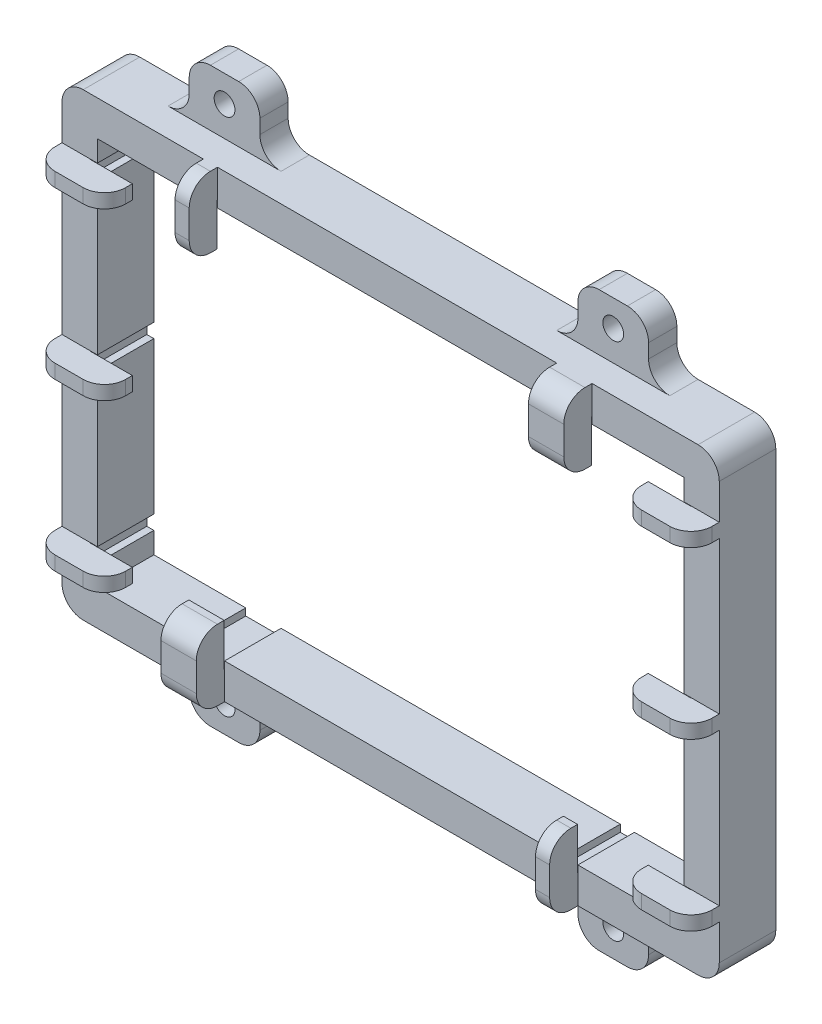
SolidWorks part; units mm, degrees
ref_plane "Front Plane" through (0, 0, 0) normal (0, 0, 1) x (1, 0, 0)
ref_plane "Top Plane" through (0, 0, 0) normal (0, 1, 0) x (1, 0, 0)
ref_plane "Right Plane" through (0, 0, 0) normal (1, 0, 0) x (0, 0, -1)
sketch "Sketch1" plane through (0, 0, 0) normal (0, 0, 1) x (1, 0, 0)
  line L0 (-41.5, 29.0054) -> (-46.5, 32.5) construction
  line L1 (41.5, -27.5) -> (-41.5, -27.5)
  line L2 (41.5, -27.5) -> (41.5, 27.5)
  line L3 (41.5, 27.5) -> (-41.5, 27.5)
  line L4 (-41.5, -27.5) -> (-41.5, 27.5)
  line L5 (0, -62.4654) -> (0, 68.7423) construction
  line L6 (-81.6773, -1.5) -> (70.6517, -1.5) construction
  line L7 (46.5, -32.5) -> (-46.5, -32.5)
  line L8 (46.5, -32.5) -> (46.5, 32.5)
  line L9 (46.5, 32.5) -> (-46.5, 32.5)
  line L10 (-46.5, -32.5) -> (-46.5, 32.5)
  line L11 (46.5, -32.5) -> (41.5, -29.0054) construction
  line L12 (46.5, 32.5) -> (41.5, 29.0054) construction
  line L13 (-41.5, -29.0054) -> (-46.5, -32.5) construction
  point P0 (0, 0)
  point P6 (0, 0)
  dimension "D1" = 83
  dimension "D2" = 55
  dimension "D3" = 5
  dimension "D4" = 5
  dimension "D5" = 5
  dimension "D6" = 5
extrude "Boss-Extrude1" add sketch "Sketch1" along normal blind 8
fillet "Fillet1" radius 3 4 edges at (-46.5, -32.5, 4) (-46.5, 32.5, 4) (46.5, -32.5, 4) (46.5, 32.5, 4)
sketch "Sketch2" plane through (0, 32.5, 0) normal (0, 1, 0) x (1, 0, 0)
  line L0 (-43.5, 0) -> (-43.5, -8) construction
  line L1 (-32.5, 0) -> (-22.5, 0)
  line L2 (-32.5, 0) -> (-32.5, -4)
  line L3 (-32.5, -4) -> (-22.5, -4)
  line L4 (-22.5, 0) -> (-22.5, -4)
  line L5 (-32.5, 0) -> (-22.5, -4) construction
  line L6 (-32.5, -4) -> (-22.5, 0) construction
  line L7 (22.5, 0) -> (32.5, 0)
  line L8 (22.5, 0) -> (22.5, -4)
  line L9 (22.5, -4) -> (32.5, -4)
  line L10 (32.5, 0) -> (32.5, -4)
  line L11 (22.5, 0) -> (32.5, -4) construction
  line L12 (22.5, -4) -> (32.5, 0) construction
  line L13 (43.5, -8) -> (43.5, 0) construction
  line L16 (43.5, 0) -> (-43.5, 0) construction
  line L17 (43.5, -8) -> (-43.5, -8) construction
  point P0 (-27.5, -2)
  point P5 (27.5, -2)
  dimension "D1" = 10
  dimension "D2" = 10
  dimension "D3" = 11
  dimension "D4" = 11
  dimension "D5" = 0
  dimension "D6" = 0
  dimension "D7" = 4
  dimension "D8" = 4
extrude "Boss-Extrude6" add sketch "Sketch2" along normal blind 8
mirror "Mirror2" about plane through (0, 0, 0) normal (0, 1, 0) of "Boss-Extrude6"
fillet "Fillet3" radius 3 8 edges at (32.5, -32.5, 2) (22.5, -32.5, 2) (-22.5, -32.5, 2) (-32.5, -32.5, 2) (-32.5, 32.5, 2) (-22.5, 32.5, 2) (22.5, 32.5, 2) (32.5, 32.5, 2)
sketch "Sketch9" plane through (0, 0, 4) normal (0, 0, 1) x (1, 0, 0)
  circle A1 centre (27.5, -36.7427) radius 1.47
  dimension "D1" = 2.94
extrude "Cut-Extrude1" cut sketch "Sketch9" against normal through all
mirror "Mirror3" about plane through (0, 0, 0) normal (1, 0, 0) of "Cut-Extrude1"
mirror "Mirror4" about plane through (0, 0, 0) normal (0, 1, 0) of "Mirror3"
sketch "Sketch10" plane through (0, 0, 0) normal (0, 0, -1) x (-1, 0, 0)
  line L0 (41.5, -27.5) -> (-41.5, -27.5) construction
  line L1 (-24.5, -27.5) -> (-26.5, -27.5)
  line L2 (-24.5, -27.5) -> (-24.5, -28.5)
  line L3 (-24.5, -28.5) -> (-26.5, -28.5)
  line L4 (-26.5, -27.5) -> (-26.5, -28.5)
  line L5 (-41.5, -27.5) -> (-41.5, 27.5) construction
  line L7 (23.5, -27.5) -> (28.5, -27.5)
  line L8 (23.5, -27.5) -> (23.5, -28.5)
  line L9 (23.5, -28.5) -> (28.5, -28.5)
  line L10 (28.5, -27.5) -> (28.5, -28.5)
  line L13 (41.5, 27.5) -> (41.5, -27.5) construction
  dimension "D1" = 1
  dimension "D2" = 2
  dimension "D3" = 15
  dimension "D4" = 13
  dimension "D5" = 5
  dimension "D6" = 1
fillet "Fillet4" radius 3 8 edges at (-22.5, 40.5, 2) (-32.5, 40.5, 2) (22.5, 40.5, 2) (32.5, 40.5, 2) (32.5, -40.5, 2) (22.5, -40.5, 2) (-22.5, -40.5, 2) (-32.5, -40.5, 2)
extrude "Cut-Extrude2" cut sketch "Sketch10" against normal through all
sketch "Sketch11" plane through (0, 0, 0) normal (0, 0, -1) x (-1, 0, 0)
  line L0 (41.5, 27.5) -> (26.5, 27.5) construction
  line L1 (-41.5, 27.5) -> (41.5, 27.5) construction
  line L2 (-41.5, 27.5) -> (-28.5, 27.5) construction
  line L3 (26.5, 27.5) -> (24.5, 27.5)
  line L4 (26.5, 27.5) -> (26.5, 28.5)
  line L5 (26.5, 28.5) -> (24.5, 28.5)
  line L6 (24.5, 27.5) -> (24.5, 28.5)
  line L8 (-28.5, 27.5) -> (-23.5, 27.5)
  line L9 (-28.5, 27.5) -> (-28.5, 28.5)
  line L10 (-28.5, 28.5) -> (-23.5, 28.5)
  line L11 (-23.5, 27.5) -> (-23.5, 28.5)
  dimension "D1" = 15
  dimension "D2" = 2
  dimension "D3" = 1
  dimension "D4" = 13
  dimension "D5" = 1
  dimension "D6" = 5
extrude "Cut-Extrude3" cut sketch "Sketch11" against normal through all
sketch "Sketch12" plane through (0, 0, 0) normal (0, 0, -1) x (-1, 0, 0)
  line L0 (58.5237, 0) -> (-57.2606, 0) construction
  line L6 (-41.5, -27.5) -> (-41.5, 27.5) construction
  line L11 (-42.5, 1) -> (-41.5, 1)
  line L12 (-42.5, 1) -> (-42.5, -1)
  line L13 (-42.5, -1) -> (-41.5, -1)
  line L14 (-41.5, 1) -> (-41.5, -1)
  line L15 (-42.5, 1) -> (-41.5, -1) construction
  line L16 (-42.5, -1) -> (-41.5, 1) construction
  line L17 (-41.5, -27.5) -> (-41.5, -24.5) construction
  line L18 (-41.5, 27.5) -> (-41.5, 24.5) construction
  line L19 (-41.5, -24.5) -> (-42.5, -24.5)
  line L20 (-41.5, -24.5) -> (-41.5, -22.5)
  line L21 (-41.5, -22.5) -> (-42.5, -22.5)
  line L22 (-42.5, -24.5) -> (-42.5, -22.5)
  line L24 (-41.5, 24.5) -> (-42.5, 24.5)
  line L25 (-41.5, 24.5) -> (-41.5, 22.5)
  line L26 (-41.5, 22.5) -> (-42.5, 22.5)
  line L27 (-42.5, 24.5) -> (-42.5, 22.5)
  point P3 (-42, 0)
  dimension "D1" = 2
  dimension "D2" = 1
  dimension "D3" = 3
  dimension "D4" = 1
  dimension "D5" = 2
  dimension "D6" = 3
  dimension "D7" = 1
  dimension "D8" = 2
extrude "Cut-Extrude4" cut sketch "Sketch12" against normal through all
mirror "Mirror5" about plane through (0, 0, 0) normal (1, 0, 0) of "Cut-Extrude4"
sketch "Sketch14" plane through (0, 0, 8) normal (0, 0, 1) x (1, 0, 0)
  line L0 (46.5, -29.5) -> (46.5, 29.5) construction
  line L1 (42.5, 22.5) -> (46.5, 22.5)
  line L2 (42.5, 22.5) -> (42.5, 24.5)
  line L3 (42.5, 24.5) -> (46.5, 24.5)
  line L4 (46.5, 22.5) -> (46.5, 24.5)
  line L6 (42.5, -1) -> (46.5, -1)
  line L7 (42.5, -1) -> (42.5, 1)
  line L8 (42.5, 1) -> (46.5, 1)
  line L9 (46.5, -1) -> (46.5, 1)
  line L10 (42.5, -24.5) -> (46.5, -24.5)
  line L11 (42.5, -24.5) -> (42.5, -22.5)
  line L12 (42.5, -22.5) -> (46.5, -22.5)
  line L13 (46.5, -24.5) -> (46.5, -22.5)
  dimension "D1" = 2
  dimension "D2" = 2
  dimension "D3" = 2
extrude "Boss-Extrude14" add sketch "Sketch14" along normal blind 4
mirror "Mirror6" about plane through (0, 0, 0) normal (1, 0, 0) of "Boss-Extrude14"
sketch "Sketch15" plane through (42.5, 0, 0) normal (-1, 0, 0) x (0, 0, 1)
  line L0 (8, 24.5) -> (0, 24.5) construction
  line L5 (8.05, 24.5) -> (12, 24.5)
  line L6 (8.05, 24.5) -> (8.05, 22.5)
  line L7 (8.05, 22.5) -> (12, 22.5)
  line L8 (12, 24.5) -> (12, 22.5)
  line L14 (12, -1) -> (8, -1) construction
  line L15 (12, 1) -> (8.05, 1)
  line L16 (12, 1) -> (12, -1)
  line L17 (12, -1) -> (8.05, -1)
  line L18 (8.05, 1) -> (8.05, -1)
  line L19 (12, -24.5) -> (8, -24.5) construction
  line L20 (12, -22.5) -> (8.05, -22.5)
  line L21 (12, -22.5) -> (12, -24.5)
  line L22 (12, -24.5) -> (8.05, -24.5)
  line L23 (8.05, -22.5) -> (8.05, -24.5)
  dimension "D1" = 3.95
  dimension "D2" = 3.95
  dimension "D3" = 3.95
extrude "Boss-Extrude18" add sketch "Sketch15" along normal blind 6
mirror "Mirror7" about plane through (0, 0, 0) normal (1, 0, 0) of "Boss-Extrude18"
sketch "Sketch16" plane through (0, 0, 8) normal (0, 0, 1) x (1, 0, 0)
  line L0 (43.5, 32.5) -> (-43.5, 32.5) construction
  line L1 (-26.5, 28.5) -> (-24.5, 28.5)
  line L2 (-26.5, 28.5) -> (-26.5, 32.5)
  line L3 (-26.5, 32.5) -> (-24.5, 32.5)
  line L4 (-24.5, 28.5) -> (-24.5, 32.5)
  line L5 (-43.5, -32.5) -> (43.5, -32.5) construction
  line L6 (23.5, 28.5) -> (28.5, 28.5)
  line L7 (23.5, 28.5) -> (23.5, 32.5)
  line L8 (23.5, 32.5) -> (28.5, 32.5)
  line L9 (28.5, 28.5) -> (28.5, 32.5)
  line L10 (26.5, -28.5) -> (24.5, -28.5)
  line L11 (26.5, -28.5) -> (26.5, -32.5)
  line L12 (26.5, -32.5) -> (24.5, -32.5)
  line L13 (24.5, -28.5) -> (24.5, -32.5)
  line L15 (-28.5, -28.5) -> (-23.5, -28.5)
  line L16 (-28.5, -28.5) -> (-28.5, -32.5)
  line L17 (-28.5, -32.5) -> (-23.5, -32.5)
  line L18 (-23.5, -28.5) -> (-23.5, -32.5)
extrude "Boss-Extrude19" add sketch "Sketch16" along normal blind 4
sketch "Sketch17" plane through (0, 28.5, 0) normal (0, -1, 0) x (1, 0, 0)
  line L0 (-24.5, 12) -> (-24.5, 8) construction
  line L1 (-26.5, 12) -> (-24.5, 12)
  line L2 (-26.5, 12) -> (-26.5, 8.05)
  line L3 (-26.5, 8.05) -> (-24.5, 8.05)
  line L4 (-24.5, 12) -> (-24.5, 8.05)
  line L5 (28.5, 12) -> (28.5, 8) construction
  line L6 (23.5, 12) -> (28.5, 12)
  line L7 (23.5, 12) -> (23.5, 8.05)
  line L8 (23.5, 8.05) -> (28.5, 8.05)
  line L9 (28.5, 12) -> (28.5, 8.05)
  dimension "D1" = 3.95
  dimension "D2" = 3.95
extrude "Boss-Extrude20" add sketch "Sketch17" along normal blind 6
sketch "Sketch18" plane through (0, -28.5, 0) normal (0, 1, 0) x (1, 0, 0)
  line L0 (-28.5, -12) -> (-28.5, -8) construction
  line L1 (-23.5, -12) -> (-28.5, -12)
  line L2 (-23.5, -12) -> (-23.5, -8.05)
  line L3 (-23.5, -8.05) -> (-28.5, -8.05)
  line L4 (-28.5, -12) -> (-28.5, -8.05)
  line L5 (24.5, -12) -> (24.5, -8) construction
  line L6 (26.5, -12) -> (24.5, -12)
  line L7 (26.5, -12) -> (26.5, -8.05)
  line L8 (26.5, -8.05) -> (24.5, -8.05)
  line L9 (24.5, -12) -> (24.5, -8.05)
  dimension "D1" = 3.95
  dimension "D2" = 3.95
extrude "Boss-Extrude21" add sketch "Sketch18" along normal blind 6
fillet "Fillet6" radius 3 20 edges at (-25.5, 32.5, 12) (-25.5, 22.5, 12) (-46.5, 23.5, 12) (-36.5, 23.5, 12) (-46.5, 0, 12) (-36.5, 0, 12) (-46.5, -23.5, 12) (-36.5, -23.5, 12) (-26, -32.5, 12) (-26, -22.5, 12) (25.5, -32.5, 12) (25.5, -22.5, 12) (36.5, -23.5, 12) (46.5, -23.5, 12) (46.5, 0, 12) (36.5, 0, 12) (36.5, 23.5, 12) (26, 22.5, 12) (26, 32.5, 12) (46.5, 23.5, 12)
